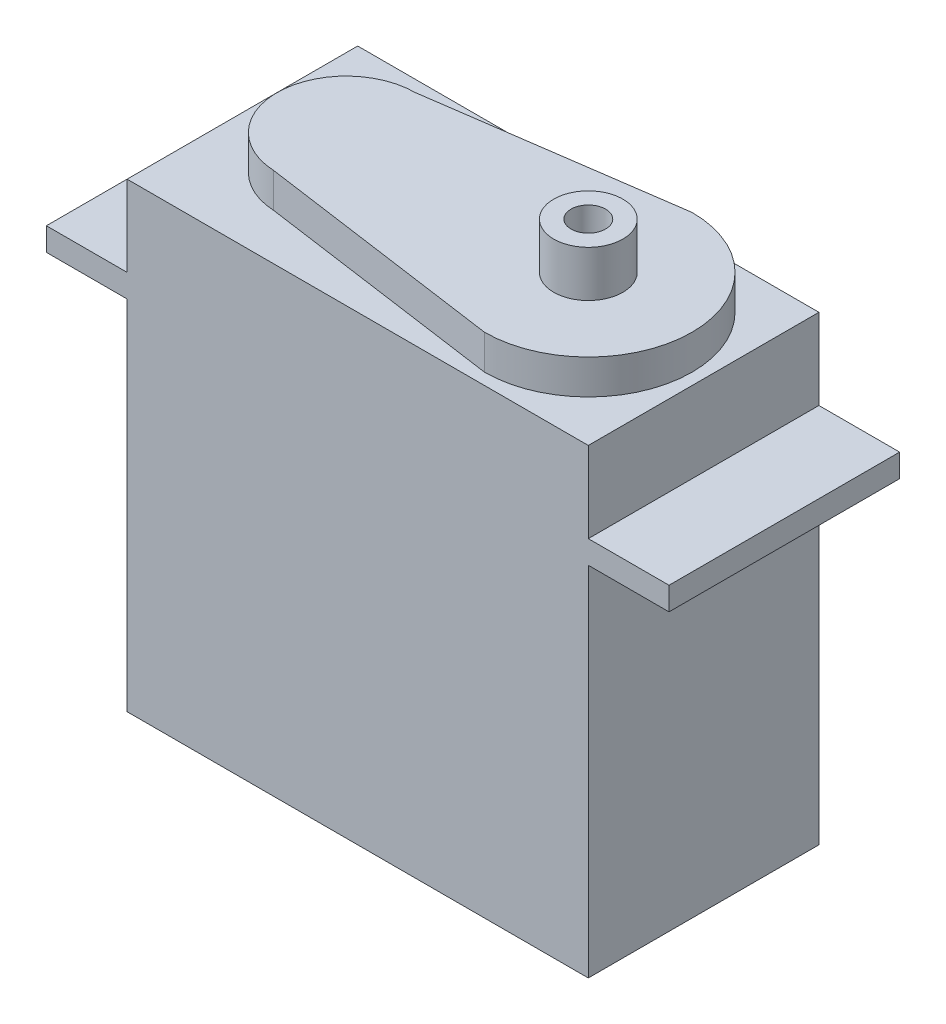
SolidWorks part; units mm, degrees
ref_plane "前视基准面" through (0, 0, 0) normal (0, 0, 1) x (1, 0, 0)
ref_plane "上视基准面" through (0, 0, 0) normal (0, 1, 0) x (1, 0, 0)
ref_plane "右视基准面" through (0, 0, 0) normal (1, 0, 0) x (0, 0, -1)
sketch "草图1" plane through (0, 0, 0) normal (0, 0, 1) x (1, 0, 0)
  line L1 (-20, 20) -> (20, 20)
  line L2 (-20, 20) -> (-20, -20)
  line L3 (-20, -20) -> (20, -20)
  line L4 (20, 20) -> (20, -20)
  line L5 (-20, 20) -> (20, -20) construction
  line L6 (-20, -20) -> (20, 20) construction
  point P0 (0, 0)
  dimension "D1" = 40
  dimension "D2" = 40
extrude "凸台-拉伸1" add sketch "草图1" along normal blind 20
sketch "草图2" plane through (0, 20, 0) normal (0, 1, 0) x (1, 0, 0)
  line L3 (20, -20) -> (20, 0) construction
  line L4 (-20, -20) -> (-20, 0) construction
  line L5 (10, -1) -> (-11, -4)
  line L6 (-11.2901, -15.993) -> (10, -19)
  arc A0 (10, -19) -> (10, -1) centre (10, -10) ccw
  arc A1 (-11, -4) -> (-11.2901, -15.993) centre (-11, -10) ccw
  point P7 (19, -10)
  point P10 (10, -10)
  point P13 (-17, -10)
  point P16 (-11, -10)
  dimension "D2" = 1
  dimension "D3" = 9
  dimension "D4" = 3
  dimension "D5" = 6
extrude "凸台-拉伸2" add sketch "草图2" along normal blind 3 contours L5 A1 L6 A0
sketch "草图5" plane through (0, 23, 0) normal (0, 1, 0) x (1, 0, 0)
  line L0 (-23.0759, -10) -> (28.1102, -10) construction
  line L1 (20, 0) -> (-20, 0) construction
  line L2 (20, -20) -> (20, 0) construction
  circle A0 centre (10, -10) radius 3
  circle A1 centre (10, -10) radius 1.5
  point P4 (10, -10)
  dimension "D1" = 10
  dimension "D2" = 10
extrude "凸台-拉伸3" add sketch "草图5" along normal blind 4
sketch "草图6" plane through (0, 0, 0) normal (0, 0, -1) x (-1, 0, 0)
  line L0 (-20, -20) -> (-20, 20) construction
  line L1 (-20, 13) -> (-27, 13)
  line L2 (-20, 13) -> (-20, 11)
  line L3 (-20, 11) -> (-27, 11)
  line L4 (-27, 13) -> (-27, 11)
  line L5 (-20, 20) -> (20, 20) construction
  line L6 (20, 20) -> (20, -20) construction
  line L7 (20, 13) -> (27, 13)
  line L8 (20, 13) -> (20, 11)
  line L9 (20, 11) -> (27, 11)
  line L10 (27, 13) -> (27, 11)
  dimension "D1" = 7
  dimension "D2" = 7
  dimension "D3" = 2
  dimension "D4" = 7
  dimension "D5" = 2
  dimension "D6" = 7
extrude "凸台-拉伸4" add sketch "草图6" against normal blind 20
ref_axis "基准轴Sevo" through (10, 27, 10) along (0, -1, 0)
